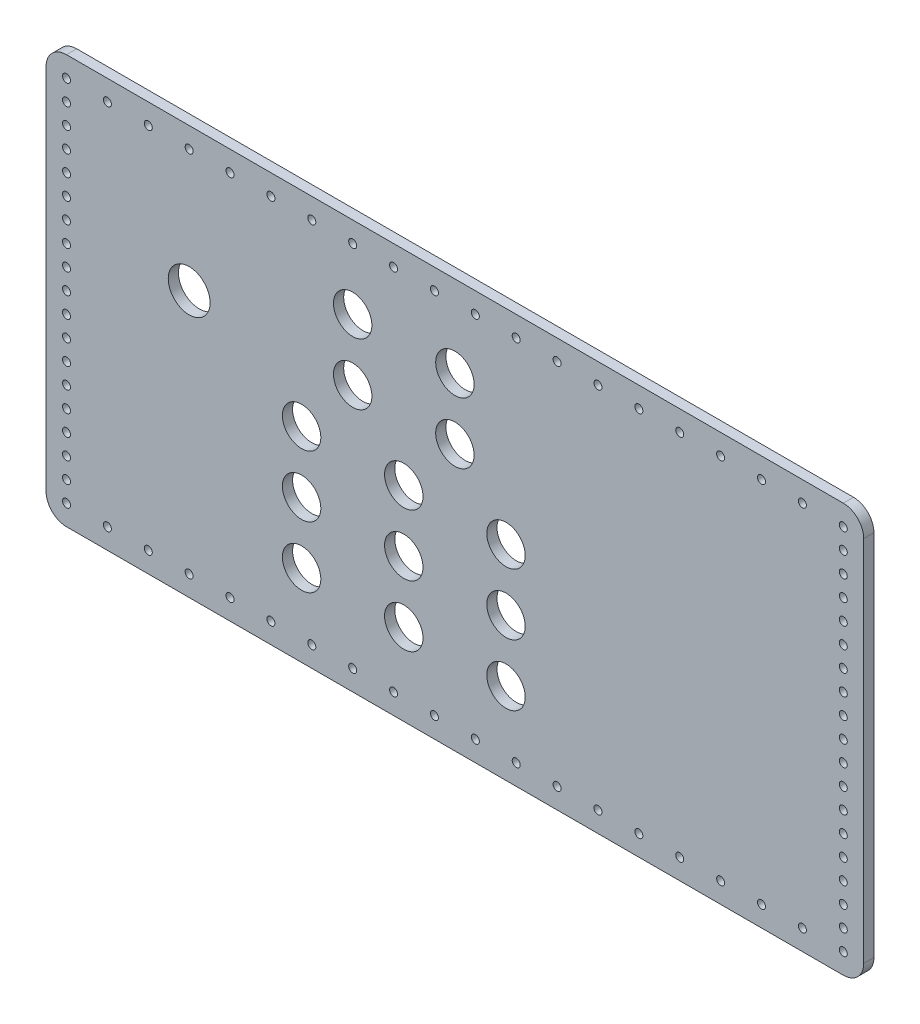
SolidWorks part; units mm, degrees
material "PC High Viscosity"
ref_plane "Front Plane" through (0, 0, 0) normal (0, 0, 1) x (1, 0, 0)
ref_plane "Top Plane" through (0, 0, 0) normal (0, 1, 0) x (1, 0, 0)
ref_plane "Right Plane" through (0, 0, 0) normal (1, 0, 0) x (0, 0, -1)
sketch "Sketch1" plane through (0, 0, 0) normal (0, 0, 1) x (1, 0, 0)
  line L1 (0, 0) -> (508, 0)
  line L2 (0, 0) -> (0, 254)
  line L3 (0, 254) -> (508, 254)
  line L4 (508, 0) -> (508, 254)
  dimension "D1" = 508
  dimension "D2" = 254
extrude "Boss-Extrude1" add sketch "Sketch1" along normal blind 6.35
sketch "Sketch3" plane through (0, 0, 0) normal (0, 0, -1) x (-1, 0, 0)
  line L0 (0, 0) -> (-508, 0) construction
  line L11 (-508, 254) -> (0, 254) construction
  line L17 (0, 254) -> (0, 0) construction
  line L18 (-508, 0) -> (-508, 254) construction
  line L19 (0, 254) -> (-25.4, 254) construction
  line L20 (0, 254) -> (0, 0) construction
  line L21 (0, 0) -> (-25.4, 0) construction
  line L22 (-25.4, 254) -> (-25.4, 0) construction
  line L23 (-508, 0) -> (-25.4, 0) construction
  line L24 (-508, 0) -> (-508, 25.4) construction
  line L25 (-508, 25.4) -> (-25.4, 25.4) construction
  line L26 (-25.4, 0) -> (-25.4, 25.4) construction
  line L27 (-508, 254) -> (-25.4, 254) construction
  line L28 (-508, 254) -> (-508, 228.6) construction
  line L29 (-508, 228.6) -> (-25.4, 228.6) construction
  line L30 (-25.4, 254) -> (-25.4, 228.6) construction
  circle A8 centre (-158.75, 88.9) radius 11.938
  circle A10 centre (-222.25, 88.9) radius 11.938
  circle A11 centre (-158.75, 50.8) radius 11.938
  circle A13 centre (-222.25, 50.8) radius 11.938
  circle A15 centre (-222.25, 127) radius 11.938
  circle A16 centre (-285.75, 127) radius 11.938
  circle A17 centre (-285.75, 88.9) radius 11.938
  circle A18 centre (-285.75, 50.8) radius 11.938
  circle A19 centre (-254, 203.2) radius 11.938
  circle A20 centre (-190.5, 203.2) radius 11.938
  circle A21 centre (-158.75, 127) radius 11.938
  circle A23 centre (-190.5, 165.1) radius 11.938
  circle A24 centre (-254, 165.1) radius 11.938
  circle A27 centre (-88.9, 165.1) radius 13
  circle A28 centre (-88.9, 165.1) radius 49.25 construction
  point P43 (-369.38, 228.6)
  dimension "D2" = 23.876
  dimension "D3" = 63.5
  dimension "D4" = 38.1
  dimension "D5" = 38.1
  dimension "D6" = 63.5
  dimension "D7" = 25.4
  dimension "D8" = 38.1
  dimension "D9" = 38.1
  dimension "D10" = 25.4
  dimension "D11" = 23.876
  dimension "D12" = 63.5
  dimension "D13" = 26
  dimension "D14" = 98.5
  dimension "D15" = 31.75
  dimension "D16" = 50.8
  dimension "D17" = 25.4
  dimension "D18" = 88.9
  dimension "D19" = 88.9
  dimension "D20" = 254
extrude "Cut-Extrude2" cut sketch "Sketch3" against normal through all contours A18 | A17 | A16 | A24 | A10 | A8 | A23 | A11 | A13 | A15 | A21 | A27 | A20 | A19 region at (158.75, 88.9, 0) region at (222.25, 88.9, 0) region at (158.75, 50.8, 0) region at (222.25, 50.8, 0) region at (285.75, 127, 0) region at (285.75, 88.9, 0) region at (285.75, 50.8, 0) region at (190.5, 165.1, 0) region at (254, 165.1, 0)
sketch "Sketch4" plane through (0, 0, 0) normal (0, 0, -1) x (-1, 0, 0)
  line L0 (0, 254) -> (0, 0) construction
  line L1 (-508, 254) -> (0, 254) construction
  line L2 (-12.7, 241.3) -> (-38.1, 241.3) construction
  line L3 (-495.3, 241.3) -> (-495.3, 228.6) construction
  line L4 (-495.3, 12.7) -> (-469.9, 12.7) construction
  circle A0 centre (-12.7, 241.3) radius 2.4892
  circle A1 centre (-38.1, 241.3) radius 2.4892
  circle A2 centre (-63.5, 241.3) radius 2.4892
  circle A3 centre (-88.9, 241.3) radius 2.4892
  circle A4 centre (-114.3, 241.3) radius 2.4892
  circle A5 centre (-139.7, 241.3) radius 2.4892
  circle A6 centre (-165.1, 241.3) radius 2.4892
  circle A7 centre (-190.5, 241.3) radius 2.4892
  circle A8 centre (-215.9, 241.3) radius 2.4892
  circle A9 centre (-241.3, 241.3) radius 2.4892
  circle A10 centre (-266.7, 241.3) radius 2.4892
  circle A11 centre (-292.1, 241.3) radius 2.4892
  circle A12 centre (-317.5, 241.3) radius 2.4892
  circle A13 centre (-342.9, 241.3) radius 2.4892
  circle A14 centre (-368.3, 241.3) radius 2.4892
  circle A15 centre (-393.7, 241.3) radius 2.4892
  circle A16 centre (-419.1, 241.3) radius 2.4892
  circle A17 centre (-444.5, 241.3) radius 2.4892
  circle A18 centre (-469.9, 241.3) radius 2.4892
  circle A19 centre (-495.3, 241.3) radius 2.4892
  circle A20 centre (-495.3, 228.6) radius 2.4892
  circle A21 centre (-12.7, 228.6) radius 2.4892
  circle A22 centre (-495.3, 215.9) radius 2.4892
  circle A23 centre (-12.7, 215.9) radius 2.4892
  circle A24 centre (-495.3, 203.2) radius 2.4892
  circle A25 centre (-12.7, 203.2) radius 2.4892
  circle A26 centre (-495.3, 190.5) radius 2.4892
  circle A27 centre (-12.7, 190.5) radius 2.4892
  circle A28 centre (-495.3, 177.8) radius 2.4892
  circle A29 centre (-12.7, 177.8) radius 2.4892
  circle A30 centre (-495.3, 165.1) radius 2.4892
  circle A31 centre (-12.7, 165.1) radius 2.4892
  circle A32 centre (-495.3, 152.4) radius 2.4892
  circle A33 centre (-12.7, 152.4) radius 2.4892
  circle A34 centre (-495.3, 139.7) radius 2.4892
  circle A35 centre (-12.7, 139.7) radius 2.4892
  circle A36 centre (-495.3, 127) radius 2.4892
  circle A37 centre (-12.7, 127) radius 2.4892
  circle A38 centre (-495.3, 114.3) radius 2.4892
  circle A39 centre (-12.7, 114.3) radius 2.4892
  circle A40 centre (-495.3, 101.6) radius 2.4892
  circle A41 centre (-12.7, 101.6) radius 2.4892
  circle A42 centre (-495.3, 88.9) radius 2.4892
  circle A43 centre (-12.7, 88.9) radius 2.4892
  circle A44 centre (-495.3, 76.2) radius 2.4892
  circle A45 centre (-12.7, 76.2) radius 2.4892
  circle A46 centre (-495.3, 63.5) radius 2.4892
  circle A47 centre (-12.7, 63.5) radius 2.4892
  circle A48 centre (-495.3, 50.8) radius 2.4892
  circle A49 centre (-12.7, 50.8) radius 2.4892
  circle A50 centre (-495.3, 38.1) radius 2.4892
  circle A51 centre (-12.7, 38.1) radius 2.4892
  circle A52 centre (-495.3, 25.4) radius 2.4892
  circle A53 centre (-12.7, 25.4) radius 2.4892
  circle A54 centre (-495.3, 12.7) radius 2.4892
  circle A55 centre (-12.7, 12.7) radius 2.4892
  circle A56 centre (-469.9, 12.7) radius 2.4892
  circle A57 centre (-444.5, 12.7) radius 2.4892
  circle A58 centre (-419.1, 12.7) radius 2.4892
  circle A59 centre (-393.7, 12.7) radius 2.4892
  circle A60 centre (-368.3, 12.7) radius 2.4892
  circle A61 centre (-342.9, 12.7) radius 2.4892
  circle A62 centre (-317.5, 12.7) radius 2.4892
  circle A63 centre (-292.1, 12.7) radius 2.4892
  circle A64 centre (-266.7, 12.7) radius 2.4892
  circle A65 centre (-241.3, 12.7) radius 2.4892
  circle A66 centre (-215.9, 12.7) radius 2.4892
  circle A67 centre (-190.5, 12.7) radius 2.4892
  circle A68 centre (-165.1, 12.7) radius 2.4892
  circle A69 centre (-139.7, 12.7) radius 2.4892
  circle A70 centre (-114.3, 12.7) radius 2.4892
  circle A71 centre (-88.9, 12.7) radius 2.4892
  circle A72 centre (-63.5, 12.7) radius 2.4892
  circle A73 centre (-38.1, 12.7) radius 2.4892
  dimension "D1" = 4.9784
  dimension "D2" = 12.7
  dimension "D3" = 12.7
  dimension "D5" = 25.4
  dimension "D7" = 12.7
  dimension "D9" = 25.4
  dimension "D4" = 20
  dimension "D6" = 19
  dimension "D8" = 19
extrude "Cut-Extrude3" cut sketch "Sketch4" against normal through all
fillet "Fillet1" radius 12.7 4 edges at (508, 0, 3.175) (0, 0, 3.175) (0, 254, 3.175) (508, 254, 3.175)
